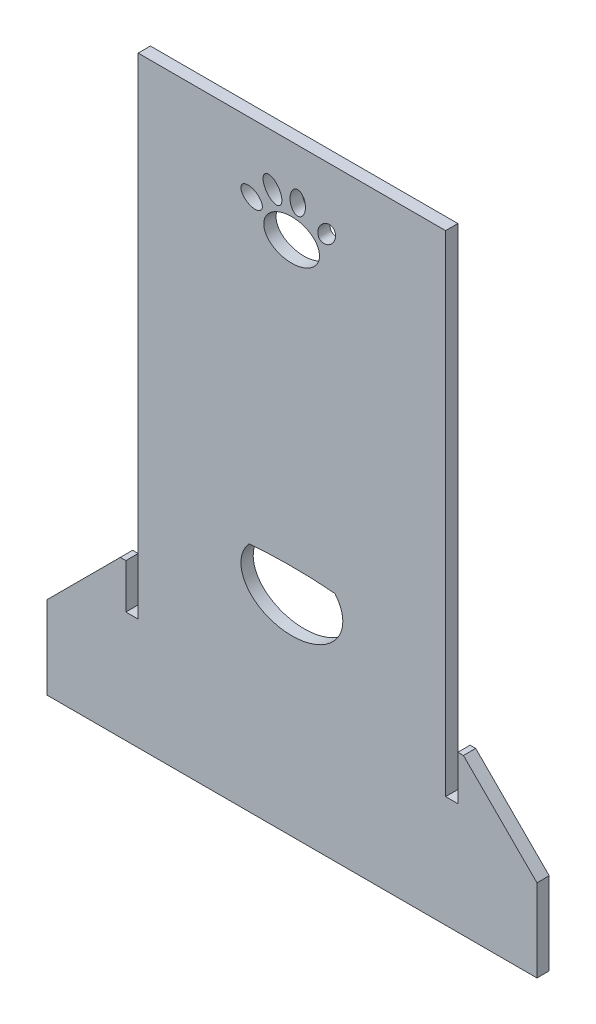
SolidWorks part; units mm, degrees
ref_plane "前基準面" through (0, 0, 0) normal (0, 0, 1) x (1, 0, 0)
ref_plane "上基準面" through (0, 0, 0) normal (0, 1, 0) x (1, 0, 0)
ref_plane "右基準面" through (0, 0, 0) normal (1, 0, 0) x (0, 0, -1)
sketch "草圖1" plane through (0, 0, 0) normal (0, 0, 1) x (1, 0, 0)
  line L0 (69, 270) -> (69, 0) construction
  line L1 (0, 0) -> (138, 0)
  line L2 (0, 0) -> (0, 270)
  line L3 (0, 270) -> (138, 270)
  line L4 (138, 0) -> (138, 270)
  line L5 (0, 70) -> (-8, 70)
  line L6 (-8, 70) -> (-41, 37)
  line L7 (-41, 37) -> (-41, 0)
  line L8 (-41, 0) -> (179, 0)
  line L9 (179, 37) -> (179, 0)
  line L10 (146, 70) -> (179, 37)
  line L11 (138, 70) -> (146, 70)
  dimension "D1" = 69
  dimension "D2" = 270
  dimension "D3" = 110
  dimension "D4" = 8
  dimension "D5" = 135
  dimension "D6" = 70
extrude "填料-伸長1" add sketch "草圖1" along normal blind 5.5 contours L7 L8 L2 L5 L6 | L0 L3 L2 L1 | L3 L0 L1 L4 | L11 L4 L8 L9 L10 region at (103.5, 135, 0) region at (34.5, 135, 0) region at (-18.2756, 29.3806, 0) region at (156.2756, 29.3806, 0)
sketch "草圖2" plane through (0, 0, 10) normal (0, 0, 1) x (1, 0, 0)
  ellipse E0 centre (68.8932, 231.8405) end of major axis (81.4041, 231.8405) minor radius 9.0504
  ellipse E1 centre (50.9249, 239.4598) end of major axis (55.4285, 236.8953) minor radius 3.4523
  ellipse E2 centre (60.2983, 247.1193) end of major axis (57.2405, 251.8606) minor radius 3.4523
  ellipse E3 centre (71.6295, 247.6014) end of major axis (71.6295, 242.4597) minor radius 3.4523
  ellipse E4 centre (84.6209, 241.9595) end of major axis (81.6773, 238.2329) minor radius 3.4523
  point P7 (0, 0)
  point P19 (0, 0)
extrude "除料-伸長1" cut sketch "草圖2" against normal through all contours E0 | E1 | E2 | E3 | E4 region at (68.8932, 231.8405, 10) region at (50.9249, 239.4598, 10) region at (60.2983, 247.1193, 10) region at (71.6295, 247.6014, 10) region at (84.6209, 241.9595, 10)
sketch "草圖3" plane through (0, 0, 5.5) normal (0, 0, 1) x (1, 0, 0)
  line L0 (0, 70) -> (-8, 70) construction
  line L1 (-5.5, 70) -> (0, 70)
  line L2 (-5.5, 70) -> (-5.5, 50)
  line L3 (-5.5, 50) -> (0, 50)
  line L4 (0, 70) -> (0, 50)
  line L5 (138, 70) -> (146, 70) construction
  line L6 (138, 70) -> (143.5, 70)
  line L7 (138, 70) -> (138, 50)
  line L8 (138, 50) -> (143.5, 50)
  line L9 (143.5, 70) -> (143.5, 50)
  line L10 (-41, 0) -> (179, 0) construction
  line L11 (0, 70) -> (0, 270) construction
  line L12 (138, 70) -> (138, 270) construction
  dimension "D1" = 5.5
  dimension "D2" = 5.5
  dimension "D3" = 50
  dimension "D4" = 50
extrude "除料-伸長2" cut sketch "草圖3" against normal through all
sketch "草圖4" plane through (0, 0, 5.5) normal (0, 0, 1) x (1, 0, 0)
  line L0 (69, 0) -> (69, 270) construction
  line L1 (-41, 0) -> (179, 0) construction
  line L2 (0, 270) -> (138, 270) construction
  ellipse E0 centre (69, 95) end of major axis (91.8568, 95) minor radius 17.0017 (49.7025, 104.1113) -> (88.2975, 104.1113) ccw
  ellipse E2 centre (69, 95) end of major axis (116.7255, 95) minor radius 9.962 (88.2975, 104.1113) -> (49.7025, 104.1113) ccw
  point P8 (69, 82.9983)
  point P13 (46.1432, 100)
  dimension "D1" = 95
extrude "除料-伸長3" cut sketch "草圖4" against normal through all and the other way through all
